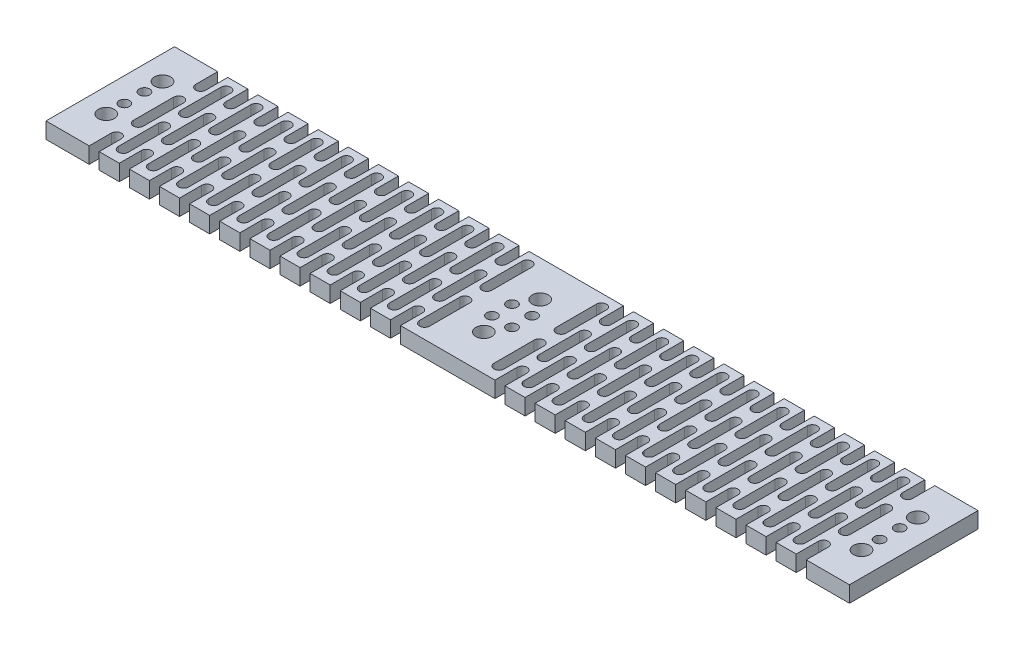
SolidWorks part; units mm, degrees
ref_plane "정면" through (0, 0, 0) normal (0, 0, 1) x (1, 0, 0)
ref_plane "윗면" through (0, 0, 0) normal (0, 1, 0) x (1, 0, 0)
ref_plane "우측면" through (0, 0, 0) normal (1, 0, 0) x (0, 0, -1)
sketch "스케치1" plane through (0, 0, 0) normal (0, 1, 0) x (1, 0, 0)
  line L1 (-50, 8) -> (50, 8)
  line L2 (-50, 8) -> (-50, -8)
  line L3 (-50, -8) -> (50, -8)
  line L4 (50, 8) -> (50, -8)
  dimension "D3" = 50
  dimension "D1" = 16
  dimension "D2" = 100
  dimension "D4" = 8
extrude "보스-돌출1" add sketch "스케치1" along normal blind 2 contours L1 L4 L3 L2
sketch "스케치2" plane through (0, 2, 0) normal (0, 1, 0) x (1, 0, 0)
  line L4 (50, 8) -> (50, -8) construction
  line L5 (-52.7608, 0) -> (58.8086, 0) construction
  line L6 (0, 14.085) -> (0, -13.5662) construction
  circle A2 centre (47, 3.5) radius 1
  circle A3 centre (0, 3.5) radius 1
  circle A4 centre (-47, 3.5) radius 1
  circle A8 centre (47, 1.25) radius 0.65
  circle A11 centre (-47, 1.25) radius 0.65
  circle A12 centre (47, -6.5) radius 1 [skipped]
  circle A13 centre (0, -6.5) radius 1 [skipped]
  circle A14 centre (-47, -6.5) radius 1 [skipped]
  circle A16 centre (1.25, 1.25) radius 0.65
  circle A17 centre (-1.25, 1.25) radius 0.65
  circle A18 centre (47, -1.25) radius 0.65
  circle A19 centre (47, -3.5) radius 1
  circle A20 centre (-1.25, -1.25) radius 0.65
  circle A21 centre (1.25, -1.25) radius 0.65
  circle A22 centre (0, -3.5) radius 1
  circle A23 centre (-47, -1.25) radius 0.65
  circle A24 centre (-47, -3.5) radius 1
  dimension "D4" = 2
  dimension "D9" = 1.3
  dimension "D11" = 2
  dimension "D5" = 3
  dimension "D6" = 3.5
  dimension "D10" = 1.25
  dimension "D12" = 2
  dimension "D7" = 3
  dimension "D8" = 2
extrude "컷-돌출1" cut sketch "스케치2" against normal through all
sketch "스케치3" plane through (0, 2, 0) normal (0, 1, 0) x (1, 0, 0)
  line L0 (44, 2.5) -> (44, -2.5) construction
  line L1 (44.625, 2.5) -> (44.625, -2.5)
  line L2 (43.375, 2.5) -> (43.375, -2.5)
  line L3 (-50, 8) -> (50, 8) construction
  line L4 (50, 8) -> (50, -8) construction
  line L5 (40.25, 2.5) -> (40.25, -2.5) construction
  line L6 (40.875, 2.5) -> (40.875, -2.5)
  line L7 (39.625, 2.5) -> (39.625, -2.5)
  line L8 (36.5, 2.5) -> (36.5, -2.5) construction
  line L9 (37.125, 2.5) -> (37.125, -2.5)
  line L10 (35.875, 2.5) -> (35.875, -2.5)
  line L11 (32.75, 2.5) -> (32.75, -2.5) construction
  line L12 (33.375, 2.5) -> (33.375, -2.5)
  line L13 (32.125, 2.5) -> (32.125, -2.5)
  line L14 (29, 2.5) -> (29, -2.5) construction
  line L15 (29.625, 2.5) -> (29.625, -2.5)
  line L16 (28.375, 2.5) -> (28.375, -2.5)
  line L17 (25.25, 2.5) -> (25.25, -2.5) construction
  line L18 (25.875, 2.5) -> (25.875, -2.5)
  line L19 (24.625, 2.5) -> (24.625, -2.5)
  line L20 (21.5, 2.5) -> (21.5, -2.5) construction
  line L21 (22.125, 2.5) -> (22.125, -2.5)
  line L22 (20.875, 2.5) -> (20.875, -2.5)
  line L23 (17.75, 2.5) -> (17.75, -2.5) construction
  line L24 (18.375, 2.5) -> (18.375, -2.5)
  line L25 (17.125, 2.5) -> (17.125, -2.5)
  line L26 (14, 2.5) -> (14, -2.5) construction
  line L27 (14.625, 2.5) -> (14.625, -2.5)
  line L28 (13.375, 2.5) -> (13.375, -2.5)
  line L29 (10.25, 2.5) -> (10.25, -2.5) construction
  line L30 (10.875, 2.5) -> (10.875, -2.5)
  line L31 (9.625, 2.5) -> (9.625, -2.5)
  line L32 (6.5, 2.5) -> (6.5, -2.5) construction
  line L33 (7.125, 2.5) -> (7.125, -2.5)
  line L34 (5.875, 2.5) -> (5.875, -2.5)
  line L35 (40.25, 10.25) -> (40.25, 5.25) construction
  line L36 (40.875, 10.25) -> (40.875, 5.25)
  line L37 (39.625, 10.25) -> (39.625, 5.25)
  line L38 (36.5, 10.25) -> (36.5, 5.25) construction
  line L39 (37.125, 10.25) -> (37.125, 5.25)
  line L40 (35.875, 10.25) -> (35.875, 5.25)
  line L41 (32.75, 10.25) -> (32.75, 5.25) construction
  line L42 (33.375, 10.25) -> (33.375, 5.25)
  line L43 (32.125, 10.25) -> (32.125, 5.25)
  line L44 (29, 10.25) -> (29, 5.25) construction
  line L45 (29.625, 10.25) -> (29.625, 5.25)
  line L46 (28.375, 10.25) -> (28.375, 5.25)
  line L47 (25.25, 10.25) -> (25.25, 5.25) construction
  line L48 (25.875, 10.25) -> (25.875, 5.25)
  line L49 (24.625, 10.25) -> (24.625, 5.25)
  line L50 (21.5, 10.25) -> (21.5, 5.25) construction
  line L51 (22.125, 10.25) -> (22.125, 5.25)
  line L52 (20.875, 10.25) -> (20.875, 5.25)
  line L53 (17.75, 10.25) -> (17.75, 5.25) construction
  line L54 (18.375, 10.25) -> (18.375, 5.25)
  line L55 (17.125, 10.25) -> (17.125, 5.25)
  line L56 (14, 10.25) -> (14, 5.25) construction
  line L57 (14.625, 10.25) -> (14.625, 5.25)
  line L58 (13.375, 10.25) -> (13.375, 5.25)
  line L59 (10.25, 10.25) -> (10.25, 5.25) construction
  line L60 (10.875, 10.25) -> (10.875, 5.25)
  line L61 (9.625, 10.25) -> (9.625, 5.25)
  line L62 (6.5, 10.25) -> (6.5, 5.25) construction
  line L63 (7.125, 10.25) -> (7.125, 5.25)
  line L64 (5.875, 10.25) -> (5.875, 5.25)
  line L65 (44, 10.25) -> (44, 5.25) construction
  line L66 (44.625, 10.25) -> (44.625, 5.25)
  line L67 (43.375, 10.25) -> (43.375, 5.25)
  line L68 (0, 0) -> (57.0875, 0) construction
  line L69 (-52.7608, 0) -> (58.8086, 0) construction
  line L70 (44, -10.25) -> (44, -5.25) construction
  line L71 (44.625, -10.25) -> (44.625, -5.25)
  line L72 (43.375, -10.25) -> (43.375, -5.25)
  line L73 (6.5, -10.25) -> (6.5, -5.25) construction
  line L74 (7.125, -10.25) -> (7.125, -5.25)
  line L75 (5.875, -10.25) -> (5.875, -5.25)
  line L76 (10.25, -10.25) -> (10.25, -5.25) construction
  line L77 (10.875, -10.25) -> (10.875, -5.25)
  line L78 (9.625, -10.25) -> (9.625, -5.25)
  line L79 (14, -10.25) -> (14, -5.25) construction
  line L80 (14.625, -10.25) -> (14.625, -5.25)
  line L81 (13.375, -10.25) -> (13.375, -5.25)
  line L82 (17.75, -10.25) -> (17.75, -5.25) construction
  line L83 (18.375, -10.25) -> (18.375, -5.25)
  line L84 (17.125, -10.25) -> (17.125, -5.25)
  line L85 (21.5, -10.25) -> (21.5, -5.25) construction
  line L86 (22.125, -10.25) -> (22.125, -5.25)
  line L87 (20.875, -10.25) -> (20.875, -5.25)
  line L88 (25.25, -10.25) -> (25.25, -5.25) construction
  line L89 (25.875, -10.25) -> (25.875, -5.25)
  line L90 (24.625, -10.25) -> (24.625, -5.25)
  line L91 (29, -10.25) -> (29, -5.25) construction
  line L92 (29.625, -10.25) -> (29.625, -5.25)
  line L93 (28.375, -10.25) -> (28.375, -5.25)
  line L94 (32.75, -10.25) -> (32.75, -5.25) construction
  line L95 (33.375, -10.25) -> (33.375, -5.25)
  line L96 (32.125, -10.25) -> (32.125, -5.25)
  line L97 (36.5, -10.25) -> (36.5, -5.25) construction
  line L98 (37.125, -10.25) -> (37.125, -5.25)
  line L99 (35.875, -10.25) -> (35.875, -5.25)
  line L100 (40.25, -10.25) -> (40.25, -5.25) construction
  line L101 (40.875, -10.25) -> (40.875, -5.25)
  line L102 (39.625, -10.25) -> (39.625, -5.25)
  line L103 (42.125, -1.25) -> (42.125, -6.25) construction
  line L104 (42.75, -1.25) -> (42.75, -6.25)
  line L105 (41.5, -1.25) -> (41.5, -6.25)
  line L106 (38.375, -1.25) -> (38.375, -6.25) construction
  line L107 (39, -1.25) -> (39, -6.25)
  line L108 (37.75, -1.25) -> (37.75, -6.25)
  line L109 (34.625, -1.25) -> (34.625, -6.25) construction
  line L110 (35.25, -1.25) -> (35.25, -6.25)
  line L111 (34, -1.25) -> (34, -6.25)
  line L112 (30.875, -1.25) -> (30.875, -6.25) construction
  line L113 (31.5, -1.25) -> (31.5, -6.25)
  line L114 (30.25, -1.25) -> (30.25, -6.25)
  line L115 (27.125, -1.25) -> (27.125, -6.25) construction
  line L116 (27.75, -1.25) -> (27.75, -6.25)
  line L117 (26.5, -1.25) -> (26.5, -6.25)
  line L118 (23.375, -1.25) -> (23.375, -6.25) construction
  line L119 (24, -1.25) -> (24, -6.25)
  line L120 (22.75, -1.25) -> (22.75, -6.25)
  line L121 (19.625, -1.25) -> (19.625, -6.25) construction
  line L122 (20.25, -1.25) -> (20.25, -6.25)
  line L123 (19, -1.25) -> (19, -6.25)
  line L124 (15.875, -1.25) -> (15.875, -6.25) construction
  line L125 (16.5, -1.25) -> (16.5, -6.25)
  line L126 (15.25, -1.25) -> (15.25, -6.25)
  line L127 (12.125, -1.25) -> (12.125, -6.25) construction
  line L128 (12.75, -1.25) -> (12.75, -6.25)
  line L129 (11.5, -1.25) -> (11.5, -6.25)
  line L130 (8.375, -1.25) -> (8.375, -6.25) construction
  line L131 (9, -1.25) -> (9, -6.25)
  line L132 (7.75, -1.25) -> (7.75, -6.25)
  line L133 (4.625, -1.25) -> (4.625, -6.25) construction
  line L134 (5.25, -1.25) -> (5.25, -6.25)
  line L135 (4, -1.25) -> (4, -6.25)
  line L136 (38.375, 6.5) -> (38.375, 1.5) construction
  line L137 (39, 6.5) -> (39, 1.5)
  line L138 (37.75, 6.5) -> (37.75, 1.5)
  line L139 (34.625, 6.5) -> (34.625, 1.5) construction
  line L140 (35.25, 6.5) -> (35.25, 1.5)
  line L141 (34, 6.5) -> (34, 1.5)
  line L142 (30.875, 6.5) -> (30.875, 1.5) construction
  line L143 (31.5, 6.5) -> (31.5, 1.5)
  line L144 (30.25, 6.5) -> (30.25, 1.5)
  line L145 (27.125, 6.5) -> (27.125, 1.5) construction
  line L146 (27.75, 6.5) -> (27.75, 1.5)
  line L147 (26.5, 6.5) -> (26.5, 1.5)
  line L148 (23.375, 6.5) -> (23.375, 1.5) construction
  line L149 (24, 6.5) -> (24, 1.5)
  line L150 (22.75, 6.5) -> (22.75, 1.5)
  line L151 (19.625, 6.5) -> (19.625, 1.5) construction
  line L152 (20.25, 6.5) -> (20.25, 1.5)
  line L153 (19, 6.5) -> (19, 1.5)
  line L154 (15.875, 6.5) -> (15.875, 1.5) construction
  line L155 (16.5, 6.5) -> (16.5, 1.5)
  line L156 (15.25, 6.5) -> (15.25, 1.5)
  line L157 (12.125, 6.5) -> (12.125, 1.5) construction
  line L158 (12.75, 6.5) -> (12.75, 1.5)
  line L159 (11.5, 6.5) -> (11.5, 1.5)
  line L160 (8.375, 6.5) -> (8.375, 1.5) construction
  line L161 (9, 6.5) -> (9, 1.5)
  line L162 (7.75, 6.5) -> (7.75, 1.5)
  line L163 (4.625, 6.5) -> (4.625, 1.5) construction
  line L164 (5.25, 6.5) -> (5.25, 1.5)
  line L165 (4, 6.5) -> (4, 1.5)
  line L166 (42.125, 6.5) -> (42.125, 1.5) construction
  line L167 (42.75, 6.5) -> (42.75, 1.5)
  line L168 (41.5, 6.5) -> (41.5, 1.5)
  line L169 (0, 14.085) -> (0, -13.5662) construction
  line L170 (-42.125, 6.5) -> (-42.125, 1.5) construction
  line L171 (-42.75, 6.5) -> (-42.75, 1.5)
  line L172 (-41.5, 6.5) -> (-41.5, 1.5)
  line L173 (-4.625, 6.5) -> (-4.625, 1.5) construction
  line L174 (-5.25, 6.5) -> (-5.25, 1.5)
  line L175 (-4, 6.5) -> (-4, 1.5)
  line L176 (-8.375, 6.5) -> (-8.375, 1.5) construction
  line L177 (-9, 6.5) -> (-9, 1.5)
  line L178 (-7.75, 6.5) -> (-7.75, 1.5)
  line L179 (-12.125, 6.5) -> (-12.125, 1.5) construction
  line L180 (-12.75, 6.5) -> (-12.75, 1.5)
  line L181 (-11.5, 6.5) -> (-11.5, 1.5)
  line L182 (-15.875, 6.5) -> (-15.875, 1.5) construction
  line L183 (-16.5, 6.5) -> (-16.5, 1.5)
  line L184 (-15.25, 6.5) -> (-15.25, 1.5)
  line L185 (-19.625, 6.5) -> (-19.625, 1.5) construction
  line L186 (-20.25, 6.5) -> (-20.25, 1.5)
  line L187 (-19, 6.5) -> (-19, 1.5)
  line L188 (-23.375, 6.5) -> (-23.375, 1.5) construction
  line L189 (-24, 6.5) -> (-24, 1.5)
  line L190 (-22.75, 6.5) -> (-22.75, 1.5)
  line L191 (-27.125, 6.5) -> (-27.125, 1.5) construction
  line L192 (-27.75, 6.5) -> (-27.75, 1.5)
  line L193 (-26.5, 6.5) -> (-26.5, 1.5)
  line L194 (-30.875, 6.5) -> (-30.875, 1.5) construction
  line L195 (-31.5, 6.5) -> (-31.5, 1.5)
  line L196 (-30.25, 6.5) -> (-30.25, 1.5)
  line L197 (-34.625, 6.5) -> (-34.625, 1.5) construction
  line L198 (-35.25, 6.5) -> (-35.25, 1.5)
  line L199 (-34, 6.5) -> (-34, 1.5)
  line L200 (-38.375, 6.5) -> (-38.375, 1.5) construction
  line L201 (-39, 6.5) -> (-39, 1.5)
  line L202 (-37.75, 6.5) -> (-37.75, 1.5)
  line L203 (-4.625, -1.25) -> (-4.625, -6.25) construction
  line L204 (-5.25, -1.25) -> (-5.25, -6.25)
  line L205 (-4, -1.25) -> (-4, -6.25)
  line L206 (-8.375, -1.25) -> (-8.375, -6.25) construction
  line L207 (-9, -1.25) -> (-9, -6.25)
  line L208 (-7.75, -1.25) -> (-7.75, -6.25)
  line L209 (-12.125, -1.25) -> (-12.125, -6.25) construction
  line L210 (-12.75, -1.25) -> (-12.75, -6.25)
  line L211 (-11.5, -1.25) -> (-11.5, -6.25)
  line L212 (-15.875, -1.25) -> (-15.875, -6.25) construction
  line L213 (-16.5, -1.25) -> (-16.5, -6.25)
  line L214 (-15.25, -1.25) -> (-15.25, -6.25)
  line L215 (-19.625, -1.25) -> (-19.625, -6.25) construction
  line L216 (-20.25, -1.25) -> (-20.25, -6.25)
  line L217 (-19, -1.25) -> (-19, -6.25)
  line L218 (-23.375, -1.25) -> (-23.375, -6.25) construction
  line L219 (-24, -1.25) -> (-24, -6.25)
  line L220 (-22.75, -1.25) -> (-22.75, -6.25)
  line L221 (-27.125, -1.25) -> (-27.125, -6.25) construction
  line L222 (-27.75, -1.25) -> (-27.75, -6.25)
  line L223 (-26.5, -1.25) -> (-26.5, -6.25)
  line L224 (-30.875, -1.25) -> (-30.875, -6.25) construction
  line L225 (-31.5, -1.25) -> (-31.5, -6.25)
  line L226 (-30.25, -1.25) -> (-30.25, -6.25)
  line L227 (-34.625, -1.25) -> (-34.625, -6.25) construction
  line L228 (-35.25, -1.25) -> (-35.25, -6.25)
  line L229 (-34, -1.25) -> (-34, -6.25)
  line L230 (-38.375, -1.25) -> (-38.375, -6.25) construction
  line L231 (-39, -1.25) -> (-39, -6.25)
  line L232 (-37.75, -1.25) -> (-37.75, -6.25)
  line L233 (-42.125, -1.25) -> (-42.125, -6.25) construction
  line L234 (-42.75, -1.25) -> (-42.75, -6.25)
  line L235 (-41.5, -1.25) -> (-41.5, -6.25)
  line L236 (-40.25, -10.25) -> (-40.25, -5.25) construction
  line L237 (-40.875, -10.25) -> (-40.875, -5.25)
  line L238 (-39.625, -10.25) -> (-39.625, -5.25)
  line L239 (-36.5, -10.25) -> (-36.5, -5.25) construction
  line L240 (-37.125, -10.25) -> (-37.125, -5.25)
  line L241 (-35.875, -10.25) -> (-35.875, -5.25)
  line L242 (-32.75, -10.25) -> (-32.75, -5.25) construction
  line L243 (-33.375, -10.25) -> (-33.375, -5.25)
  line L244 (-32.125, -10.25) -> (-32.125, -5.25)
  line L245 (-29, -10.25) -> (-29, -5.25) construction
  line L246 (-29.625, -10.25) -> (-29.625, -5.25)
  line L247 (-28.375, -10.25) -> (-28.375, -5.25)
  line L248 (-25.25, -10.25) -> (-25.25, -5.25) construction
  line L249 (-25.875, -10.25) -> (-25.875, -5.25)
  line L250 (-24.625, -10.25) -> (-24.625, -5.25)
  line L251 (-21.5, -10.25) -> (-21.5, -5.25) construction
  line L252 (-22.125, -10.25) -> (-22.125, -5.25)
  line L253 (-20.875, -10.25) -> (-20.875, -5.25)
  line L254 (-17.75, -10.25) -> (-17.75, -5.25) construction
  line L255 (-18.375, -10.25) -> (-18.375, -5.25)
  line L256 (-17.125, -10.25) -> (-17.125, -5.25)
  line L257 (-14, -10.25) -> (-14, -5.25) construction
  line L258 (-14.625, -10.25) -> (-14.625, -5.25)
  line L259 (-13.375, -10.25) -> (-13.375, -5.25)
  line L260 (-10.25, -10.25) -> (-10.25, -5.25) construction
  line L261 (-10.875, -10.25) -> (-10.875, -5.25)
  line L262 (-9.625, -10.25) -> (-9.625, -5.25)
  line L263 (-6.5, -10.25) -> (-6.5, -5.25) construction
  line L264 (-7.125, -10.25) -> (-7.125, -5.25)
  line L265 (-5.875, -10.25) -> (-5.875, -5.25)
  line L266 (-44, -10.25) -> (-44, -5.25) construction
  line L267 (-44.625, -10.25) -> (-44.625, -5.25)
  line L268 (-43.375, -10.25) -> (-43.375, -5.25)
  line L269 (-44, 10.25) -> (-44, 5.25) construction
  line L270 (-44.625, 10.25) -> (-44.625, 5.25)
  line L271 (-43.375, 10.25) -> (-43.375, 5.25)
  line L272 (-6.5, 10.25) -> (-6.5, 5.25) construction
  line L273 (-7.125, 10.25) -> (-7.125, 5.25)
  line L274 (-5.875, 10.25) -> (-5.875, 5.25)
  line L275 (-10.25, 10.25) -> (-10.25, 5.25) construction
  line L276 (-10.875, 10.25) -> (-10.875, 5.25)
  line L277 (-9.625, 10.25) -> (-9.625, 5.25)
  line L278 (-14, 10.25) -> (-14, 5.25) construction
  line L279 (-14.625, 10.25) -> (-14.625, 5.25)
  line L280 (-13.375, 10.25) -> (-13.375, 5.25)
  line L281 (-17.75, 10.25) -> (-17.75, 5.25) construction
  line L282 (-18.375, 10.25) -> (-18.375, 5.25)
  line L283 (-17.125, 10.25) -> (-17.125, 5.25)
  line L284 (-21.5, 10.25) -> (-21.5, 5.25) construction
  line L285 (-22.125, 10.25) -> (-22.125, 5.25)
  line L286 (-20.875, 10.25) -> (-20.875, 5.25)
  line L287 (-25.25, 10.25) -> (-25.25, 5.25) construction
  line L288 (-25.875, 10.25) -> (-25.875, 5.25)
  line L289 (-24.625, 10.25) -> (-24.625, 5.25)
  line L290 (-29, 10.25) -> (-29, 5.25) construction
  line L291 (-29.625, 10.25) -> (-29.625, 5.25)
  line L292 (-28.375, 10.25) -> (-28.375, 5.25)
  line L293 (-32.75, 10.25) -> (-32.75, 5.25) construction
  line L294 (-33.375, 10.25) -> (-33.375, 5.25)
  line L295 (-32.125, 10.25) -> (-32.125, 5.25)
  line L296 (-36.5, 10.25) -> (-36.5, 5.25) construction
  line L297 (-37.125, 10.25) -> (-37.125, 5.25)
  line L298 (-35.875, 10.25) -> (-35.875, 5.25)
  line L299 (-40.25, 10.25) -> (-40.25, 5.25) construction
  line L300 (-40.875, 10.25) -> (-40.875, 5.25)
  line L301 (-39.625, 10.25) -> (-39.625, 5.25)
  line L302 (-6.5, 2.5) -> (-6.5, -2.5) construction
  line L303 (-7.125, 2.5) -> (-7.125, -2.5)
  line L304 (-5.875, 2.5) -> (-5.875, -2.5)
  line L305 (-10.25, 2.5) -> (-10.25, -2.5) construction
  line L306 (-10.875, 2.5) -> (-10.875, -2.5)
  line L307 (-9.625, 2.5) -> (-9.625, -2.5)
  line L308 (-14, 2.5) -> (-14, -2.5) construction
  line L309 (-14.625, 2.5) -> (-14.625, -2.5)
  line L310 (-13.375, 2.5) -> (-13.375, -2.5)
  line L311 (-17.75, 2.5) -> (-17.75, -2.5) construction
  line L312 (-18.375, 2.5) -> (-18.375, -2.5)
  line L313 (-17.125, 2.5) -> (-17.125, -2.5)
  line L314 (-21.5, 2.5) -> (-21.5, -2.5) construction
  line L315 (-22.125, 2.5) -> (-22.125, -2.5)
  line L316 (-20.875, 2.5) -> (-20.875, -2.5)
  line L317 (-25.25, 2.5) -> (-25.25, -2.5) construction
  line L318 (-25.875, 2.5) -> (-25.875, -2.5)
  line L319 (-24.625, 2.5) -> (-24.625, -2.5)
  line L320 (-29, 2.5) -> (-29, -2.5) construction
  line L321 (-29.625, 2.5) -> (-29.625, -2.5)
  line L322 (-28.375, 2.5) -> (-28.375, -2.5)
  line L323 (-32.75, 2.5) -> (-32.75, -2.5) construction
  line L324 (-33.375, 2.5) -> (-33.375, -2.5)
  line L325 (-32.125, 2.5) -> (-32.125, -2.5)
  line L326 (-36.5, 2.5) -> (-36.5, -2.5) construction
  line L327 (-37.125, 2.5) -> (-37.125, -2.5)
  line L328 (-35.875, 2.5) -> (-35.875, -2.5)
  line L329 (-40.25, 2.5) -> (-40.25, -2.5) construction
  line L330 (-40.875, 2.5) -> (-40.875, -2.5)
  line L331 (-39.625, 2.5) -> (-39.625, -2.5)
  line L332 (-44, 2.5) -> (-44, -2.5) construction
  line L333 (-44.625, 2.5) -> (-44.625, -2.5)
  line L334 (-43.375, 2.5) -> (-43.375, -2.5)
  arc A0 (44.625, 2.5) -> (43.375, 2.5) centre (44, 2.5) ccw
  arc A1 (43.375, -2.5) -> (44.625, -2.5) centre (44, -2.5) ccw
  arc A2 (40.875, 2.5) -> (39.625, 2.5) centre (40.25, 2.5) ccw
  arc A3 (39.625, -2.5) -> (40.875, -2.5) centre (40.25, -2.5) ccw
  arc A4 (37.125, 2.5) -> (35.875, 2.5) centre (36.5, 2.5) ccw
  arc A5 (35.875, -2.5) -> (37.125, -2.5) centre (36.5, -2.5) ccw
  arc A6 (33.375, 2.5) -> (32.125, 2.5) centre (32.75, 2.5) ccw
  arc A7 (32.125, -2.5) -> (33.375, -2.5) centre (32.75, -2.5) ccw
  arc A8 (29.625, 2.5) -> (28.375, 2.5) centre (29, 2.5) ccw
  arc A9 (28.375, -2.5) -> (29.625, -2.5) centre (29, -2.5) ccw
  arc A10 (25.875, 2.5) -> (24.625, 2.5) centre (25.25, 2.5) ccw
  arc A11 (24.625, -2.5) -> (25.875, -2.5) centre (25.25, -2.5) ccw
  arc A12 (22.125, 2.5) -> (20.875, 2.5) centre (21.5, 2.5) ccw
  arc A13 (20.875, -2.5) -> (22.125, -2.5) centre (21.5, -2.5) ccw
  arc A14 (18.375, 2.5) -> (17.125, 2.5) centre (17.75, 2.5) ccw
  arc A15 (17.125, -2.5) -> (18.375, -2.5) centre (17.75, -2.5) ccw
  arc A16 (14.625, 2.5) -> (13.375, 2.5) centre (14, 2.5) ccw
  arc A17 (13.375, -2.5) -> (14.625, -2.5) centre (14, -2.5) ccw
  arc A18 (10.875, 2.5) -> (9.625, 2.5) centre (10.25, 2.5) ccw
  arc A19 (9.625, -2.5) -> (10.875, -2.5) centre (10.25, -2.5) ccw
  arc A20 (7.125, 2.5) -> (5.875, 2.5) centre (6.5, 2.5) ccw
  arc A21 (5.875, -2.5) -> (7.125, -2.5) centre (6.5, -2.5) ccw
  arc A22 (40.875, 10.25) -> (39.625, 10.25) centre (40.25, 10.25) ccw
  arc A23 (39.625, 5.25) -> (40.875, 5.25) centre (40.25, 5.25) ccw
  arc A24 (37.125, 10.25) -> (35.875, 10.25) centre (36.5, 10.25) ccw
  arc A25 (35.875, 5.25) -> (37.125, 5.25) centre (36.5, 5.25) ccw
  arc A26 (33.375, 10.25) -> (32.125, 10.25) centre (32.75, 10.25) ccw
  arc A27 (32.125, 5.25) -> (33.375, 5.25) centre (32.75, 5.25) ccw
  arc A28 (29.625, 10.25) -> (28.375, 10.25) centre (29, 10.25) ccw
  arc A29 (28.375, 5.25) -> (29.625, 5.25) centre (29, 5.25) ccw
  arc A30 (25.875, 10.25) -> (24.625, 10.25) centre (25.25, 10.25) ccw
  arc A31 (24.625, 5.25) -> (25.875, 5.25) centre (25.25, 5.25) ccw
  arc A32 (22.125, 10.25) -> (20.875, 10.25) centre (21.5, 10.25) ccw
  arc A33 (20.875, 5.25) -> (22.125, 5.25) centre (21.5, 5.25) ccw
  arc A34 (18.375, 10.25) -> (17.125, 10.25) centre (17.75, 10.25) ccw
  arc A35 (17.125, 5.25) -> (18.375, 5.25) centre (17.75, 5.25) ccw
  arc A36 (14.625, 10.25) -> (13.375, 10.25) centre (14, 10.25) ccw
  arc A37 (13.375, 5.25) -> (14.625, 5.25) centre (14, 5.25) ccw
  arc A38 (10.875, 10.25) -> (9.625, 10.25) centre (10.25, 10.25) ccw
  arc A39 (9.625, 5.25) -> (10.875, 5.25) centre (10.25, 5.25) ccw
  arc A40 (7.125, 10.25) -> (5.875, 10.25) centre (6.5, 10.25) ccw
  arc A41 (5.875, 5.25) -> (7.125, 5.25) centre (6.5, 5.25) ccw
  arc A42 (44.625, 10.25) -> (43.375, 10.25) centre (44, 10.25) ccw
  arc A43 (43.375, 5.25) -> (44.625, 5.25) centre (44, 5.25) ccw
  arc A44 (44.625, -10.25) -> (43.375, -10.25) centre (44, -10.25) cw
  arc A45 (43.375, -5.25) -> (44.625, -5.25) centre (44, -5.25) cw
  arc A46 (7.125, -10.25) -> (5.875, -10.25) centre (6.5, -10.25) cw
  arc A47 (5.875, -5.25) -> (7.125, -5.25) centre (6.5, -5.25) cw
  arc A48 (10.875, -10.25) -> (9.625, -10.25) centre (10.25, -10.25) cw
  arc A49 (9.625, -5.25) -> (10.875, -5.25) centre (10.25, -5.25) cw
  arc A50 (14.625, -10.25) -> (13.375, -10.25) centre (14, -10.25) cw
  arc A51 (13.375, -5.25) -> (14.625, -5.25) centre (14, -5.25) cw
  arc A52 (18.375, -10.25) -> (17.125, -10.25) centre (17.75, -10.25) cw
  arc A53 (17.125, -5.25) -> (18.375, -5.25) centre (17.75, -5.25) cw
  arc A54 (22.125, -10.25) -> (20.875, -10.25) centre (21.5, -10.25) cw
  arc A55 (20.875, -5.25) -> (22.125, -5.25) centre (21.5, -5.25) cw
  arc A56 (25.875, -10.25) -> (24.625, -10.25) centre (25.25, -10.25) cw
  arc A57 (24.625, -5.25) -> (25.875, -5.25) centre (25.25, -5.25) cw
  arc A58 (29.625, -10.25) -> (28.375, -10.25) centre (29, -10.25) cw
  arc A59 (28.375, -5.25) -> (29.625, -5.25) centre (29, -5.25) cw
  arc A60 (33.375, -10.25) -> (32.125, -10.25) centre (32.75, -10.25) cw
  arc A61 (32.125, -5.25) -> (33.375, -5.25) centre (32.75, -5.25) cw
  arc A62 (37.125, -10.25) -> (35.875, -10.25) centre (36.5, -10.25) cw
  arc A63 (35.875, -5.25) -> (37.125, -5.25) centre (36.5, -5.25) cw
  arc A64 (40.875, -10.25) -> (39.625, -10.25) centre (40.25, -10.25) cw
  arc A65 (39.625, -5.25) -> (40.875, -5.25) centre (40.25, -5.25) cw
  arc A66 (42.75, -1.25) -> (41.5, -1.25) centre (42.125, -1.25) ccw
  arc A67 (41.5, -6.25) -> (42.75, -6.25) centre (42.125, -6.25) ccw
  arc A68 (39, -1.25) -> (37.75, -1.25) centre (38.375, -1.25) ccw
  arc A69 (37.75, -6.25) -> (39, -6.25) centre (38.375, -6.25) ccw
  arc A70 (35.25, -1.25) -> (34, -1.25) centre (34.625, -1.25) ccw
  arc A71 (34, -6.25) -> (35.25, -6.25) centre (34.625, -6.25) ccw
  arc A72 (31.5, -1.25) -> (30.25, -1.25) centre (30.875, -1.25) ccw
  arc A73 (30.25, -6.25) -> (31.5, -6.25) centre (30.875, -6.25) ccw
  arc A74 (27.75, -1.25) -> (26.5, -1.25) centre (27.125, -1.25) ccw
  arc A75 (26.5, -6.25) -> (27.75, -6.25) centre (27.125, -6.25) ccw
  arc A76 (24, -1.25) -> (22.75, -1.25) centre (23.375, -1.25) ccw
  arc A77 (22.75, -6.25) -> (24, -6.25) centre (23.375, -6.25) ccw
  arc A78 (20.25, -1.25) -> (19, -1.25) centre (19.625, -1.25) ccw
  arc A79 (19, -6.25) -> (20.25, -6.25) centre (19.625, -6.25) ccw
  arc A80 (16.5, -1.25) -> (15.25, -1.25) centre (15.875, -1.25) ccw
  arc A81 (15.25, -6.25) -> (16.5, -6.25) centre (15.875, -6.25) ccw
  arc A82 (12.75, -1.25) -> (11.5, -1.25) centre (12.125, -1.25) ccw
  arc A83 (11.5, -6.25) -> (12.75, -6.25) centre (12.125, -6.25) ccw
  arc A84 (9, -1.25) -> (7.75, -1.25) centre (8.375, -1.25) ccw
  arc A85 (7.75, -6.25) -> (9, -6.25) centre (8.375, -6.25) ccw
  arc A86 (5.25, -1.25) -> (4, -1.25) centre (4.625, -1.25) ccw
  arc A87 (4, -6.25) -> (5.25, -6.25) centre (4.625, -6.25) ccw
  arc A88 (39, 6.5) -> (37.75, 6.5) centre (38.375, 6.5) ccw
  arc A89 (37.75, 1.5) -> (39, 1.5) centre (38.375, 1.5) ccw
  arc A90 (35.25, 6.5) -> (34, 6.5) centre (34.625, 6.5) ccw
  arc A91 (34, 1.5) -> (35.25, 1.5) centre (34.625, 1.5) ccw
  arc A92 (31.5, 6.5) -> (30.25, 6.5) centre (30.875, 6.5) ccw
  arc A93 (30.25, 1.5) -> (31.5, 1.5) centre (30.875, 1.5) ccw
  arc A94 (27.75, 6.5) -> (26.5, 6.5) centre (27.125, 6.5) ccw
  arc A95 (26.5, 1.5) -> (27.75, 1.5) centre (27.125, 1.5) ccw
  arc A96 (24, 6.5) -> (22.75, 6.5) centre (23.375, 6.5) ccw
  arc A97 (22.75, 1.5) -> (24, 1.5) centre (23.375, 1.5) ccw
  arc A98 (20.25, 6.5) -> (19, 6.5) centre (19.625, 6.5) ccw
  arc A99 (19, 1.5) -> (20.25, 1.5) centre (19.625, 1.5) ccw
  arc A100 (16.5, 6.5) -> (15.25, 6.5) centre (15.875, 6.5) ccw
  arc A101 (15.25, 1.5) -> (16.5, 1.5) centre (15.875, 1.5) ccw
  arc A102 (12.75, 6.5) -> (11.5, 6.5) centre (12.125, 6.5) ccw
  arc A103 (11.5, 1.5) -> (12.75, 1.5) centre (12.125, 1.5) ccw
  arc A104 (9, 6.5) -> (7.75, 6.5) centre (8.375, 6.5) ccw
  arc A105 (7.75, 1.5) -> (9, 1.5) centre (8.375, 1.5) ccw
  arc A106 (5.25, 6.5) -> (4, 6.5) centre (4.625, 6.5) ccw
  arc A107 (4, 1.5) -> (5.25, 1.5) centre (4.625, 1.5) ccw
  arc A108 (42.75, 6.5) -> (41.5, 6.5) centre (42.125, 6.5) ccw
  arc A109 (41.5, 1.5) -> (42.75, 1.5) centre (42.125, 1.5) ccw
  arc A110 (-42.75, 6.5) -> (-41.5, 6.5) centre (-42.125, 6.5) cw
  arc A111 (-41.5, 1.5) -> (-42.75, 1.5) centre (-42.125, 1.5) cw
  arc A112 (-5.25, 6.5) -> (-4, 6.5) centre (-4.625, 6.5) cw
  arc A113 (-4, 1.5) -> (-5.25, 1.5) centre (-4.625, 1.5) cw
  arc A114 (-9, 6.5) -> (-7.75, 6.5) centre (-8.375, 6.5) cw
  arc A115 (-7.75, 1.5) -> (-9, 1.5) centre (-8.375, 1.5) cw
  arc A116 (-12.75, 6.5) -> (-11.5, 6.5) centre (-12.125, 6.5) cw
  arc A117 (-11.5, 1.5) -> (-12.75, 1.5) centre (-12.125, 1.5) cw
  arc A118 (-16.5, 6.5) -> (-15.25, 6.5) centre (-15.875, 6.5) cw
  arc A119 (-15.25, 1.5) -> (-16.5, 1.5) centre (-15.875, 1.5) cw
  arc A120 (-20.25, 6.5) -> (-19, 6.5) centre (-19.625, 6.5) cw
  arc A121 (-19, 1.5) -> (-20.25, 1.5) centre (-19.625, 1.5) cw
  arc A122 (-24, 6.5) -> (-22.75, 6.5) centre (-23.375, 6.5) cw
  arc A123 (-22.75, 1.5) -> (-24, 1.5) centre (-23.375, 1.5) cw
  arc A124 (-27.75, 6.5) -> (-26.5, 6.5) centre (-27.125, 6.5) cw
  arc A125 (-26.5, 1.5) -> (-27.75, 1.5) centre (-27.125, 1.5) cw
  arc A126 (-31.5, 6.5) -> (-30.25, 6.5) centre (-30.875, 6.5) cw
  arc A127 (-30.25, 1.5) -> (-31.5, 1.5) centre (-30.875, 1.5) cw
  arc A128 (-35.25, 6.5) -> (-34, 6.5) centre (-34.625, 6.5) cw
  arc A129 (-34, 1.5) -> (-35.25, 1.5) centre (-34.625, 1.5) cw
  arc A130 (-39, 6.5) -> (-37.75, 6.5) centre (-38.375, 6.5) cw
  arc A131 (-37.75, 1.5) -> (-39, 1.5) centre (-38.375, 1.5) cw
  arc A132 (-5.25, -1.25) -> (-4, -1.25) centre (-4.625, -1.25) cw
  arc A133 (-4, -6.25) -> (-5.25, -6.25) centre (-4.625, -6.25) cw
  arc A134 (-9, -1.25) -> (-7.75, -1.25) centre (-8.375, -1.25) cw
  arc A135 (-7.75, -6.25) -> (-9, -6.25) centre (-8.375, -6.25) cw
  arc A136 (-12.75, -1.25) -> (-11.5, -1.25) centre (-12.125, -1.25) cw
  arc A137 (-11.5, -6.25) -> (-12.75, -6.25) centre (-12.125, -6.25) cw
  arc A138 (-16.5, -1.25) -> (-15.25, -1.25) centre (-15.875, -1.25) cw
  arc A139 (-15.25, -6.25) -> (-16.5, -6.25) centre (-15.875, -6.25) cw
  arc A140 (-20.25, -1.25) -> (-19, -1.25) centre (-19.625, -1.25) cw
  arc A141 (-19, -6.25) -> (-20.25, -6.25) centre (-19.625, -6.25) cw
  arc A142 (-24, -1.25) -> (-22.75, -1.25) centre (-23.375, -1.25) cw
  arc A143 (-22.75, -6.25) -> (-24, -6.25) centre (-23.375, -6.25) cw
  arc A144 (-27.75, -1.25) -> (-26.5, -1.25) centre (-27.125, -1.25) cw
  arc A145 (-26.5, -6.25) -> (-27.75, -6.25) centre (-27.125, -6.25) cw
  arc A146 (-31.5, -1.25) -> (-30.25, -1.25) centre (-30.875, -1.25) cw
  arc A147 (-30.25, -6.25) -> (-31.5, -6.25) centre (-30.875, -6.25) cw
  arc A148 (-35.25, -1.25) -> (-34, -1.25) centre (-34.625, -1.25) cw
  arc A149 (-34, -6.25) -> (-35.25, -6.25) centre (-34.625, -6.25) cw
  arc A150 (-39, -1.25) -> (-37.75, -1.25) centre (-38.375, -1.25) cw
  arc A151 (-37.75, -6.25) -> (-39, -6.25) centre (-38.375, -6.25) cw
  arc A152 (-42.75, -1.25) -> (-41.5, -1.25) centre (-42.125, -1.25) cw
  arc A153 (-41.5, -6.25) -> (-42.75, -6.25) centre (-42.125, -6.25) cw
  arc A154 (-40.875, -10.25) -> (-39.625, -10.25) centre (-40.25, -10.25) ccw
  arc A155 (-39.625, -5.25) -> (-40.875, -5.25) centre (-40.25, -5.25) ccw
  arc A156 (-37.125, -10.25) -> (-35.875, -10.25) centre (-36.5, -10.25) ccw
  arc A157 (-35.875, -5.25) -> (-37.125, -5.25) centre (-36.5, -5.25) ccw
  arc A158 (-33.375, -10.25) -> (-32.125, -10.25) centre (-32.75, -10.25) ccw
  arc A159 (-32.125, -5.25) -> (-33.375, -5.25) centre (-32.75, -5.25) ccw
  arc A160 (-29.625, -10.25) -> (-28.375, -10.25) centre (-29, -10.25) ccw
  arc A161 (-28.375, -5.25) -> (-29.625, -5.25) centre (-29, -5.25) ccw
  arc A162 (-25.875, -10.25) -> (-24.625, -10.25) centre (-25.25, -10.25) ccw
  arc A163 (-24.625, -5.25) -> (-25.875, -5.25) centre (-25.25, -5.25) ccw
  arc A164 (-22.125, -10.25) -> (-20.875, -10.25) centre (-21.5, -10.25) ccw
  arc A165 (-20.875, -5.25) -> (-22.125, -5.25) centre (-21.5, -5.25) ccw
  arc A166 (-18.375, -10.25) -> (-17.125, -10.25) centre (-17.75, -10.25) ccw
  arc A167 (-17.125, -5.25) -> (-18.375, -5.25) centre (-17.75, -5.25) ccw
  arc A168 (-14.625, -10.25) -> (-13.375, -10.25) centre (-14, -10.25) ccw
  arc A169 (-13.375, -5.25) -> (-14.625, -5.25) centre (-14, -5.25) ccw
  arc A170 (-10.875, -10.25) -> (-9.625, -10.25) centre (-10.25, -10.25) ccw
  arc A171 (-9.625, -5.25) -> (-10.875, -5.25) centre (-10.25, -5.25) ccw
  arc A172 (-7.125, -10.25) -> (-5.875, -10.25) centre (-6.5, -10.25) ccw
  arc A173 (-5.875, -5.25) -> (-7.125, -5.25) centre (-6.5, -5.25) ccw
  arc A174 (-44.625, -10.25) -> (-43.375, -10.25) centre (-44, -10.25) ccw
  arc A175 (-43.375, -5.25) -> (-44.625, -5.25) centre (-44, -5.25) ccw
  arc A176 (-44.625, 10.25) -> (-43.375, 10.25) centre (-44, 10.25) cw
  arc A177 (-43.375, 5.25) -> (-44.625, 5.25) centre (-44, 5.25) cw
  arc A178 (-7.125, 10.25) -> (-5.875, 10.25) centre (-6.5, 10.25) cw
  arc A179 (-5.875, 5.25) -> (-7.125, 5.25) centre (-6.5, 5.25) cw
  arc A180 (-10.875, 10.25) -> (-9.625, 10.25) centre (-10.25, 10.25) cw
  arc A181 (-9.625, 5.25) -> (-10.875, 5.25) centre (-10.25, 5.25) cw
  arc A182 (-14.625, 10.25) -> (-13.375, 10.25) centre (-14, 10.25) cw
  arc A183 (-13.375, 5.25) -> (-14.625, 5.25) centre (-14, 5.25) cw
  arc A184 (-18.375, 10.25) -> (-17.125, 10.25) centre (-17.75, 10.25) cw
  arc A185 (-17.125, 5.25) -> (-18.375, 5.25) centre (-17.75, 5.25) cw
  arc A186 (-22.125, 10.25) -> (-20.875, 10.25) centre (-21.5, 10.25) cw
  arc A187 (-20.875, 5.25) -> (-22.125, 5.25) centre (-21.5, 5.25) cw
  arc A188 (-25.875, 10.25) -> (-24.625, 10.25) centre (-25.25, 10.25) cw
  arc A189 (-24.625, 5.25) -> (-25.875, 5.25) centre (-25.25, 5.25) cw
  arc A190 (-29.625, 10.25) -> (-28.375, 10.25) centre (-29, 10.25) cw
  arc A191 (-28.375, 5.25) -> (-29.625, 5.25) centre (-29, 5.25) cw
  arc A192 (-33.375, 10.25) -> (-32.125, 10.25) centre (-32.75, 10.25) cw
  arc A193 (-32.125, 5.25) -> (-33.375, 5.25) centre (-32.75, 5.25) cw
  arc A194 (-37.125, 10.25) -> (-35.875, 10.25) centre (-36.5, 10.25) cw
  arc A195 (-35.875, 5.25) -> (-37.125, 5.25) centre (-36.5, 5.25) cw
  arc A196 (-40.875, 10.25) -> (-39.625, 10.25) centre (-40.25, 10.25) cw
  arc A197 (-39.625, 5.25) -> (-40.875, 5.25) centre (-40.25, 5.25) cw
  arc A198 (-7.125, 2.5) -> (-5.875, 2.5) centre (-6.5, 2.5) cw
  arc A199 (-5.875, -2.5) -> (-7.125, -2.5) centre (-6.5, -2.5) cw
  arc A200 (-10.875, 2.5) -> (-9.625, 2.5) centre (-10.25, 2.5) cw
  arc A201 (-9.625, -2.5) -> (-10.875, -2.5) centre (-10.25, -2.5) cw
  arc A202 (-14.625, 2.5) -> (-13.375, 2.5) centre (-14, 2.5) cw
  arc A203 (-13.375, -2.5) -> (-14.625, -2.5) centre (-14, -2.5) cw
  arc A204 (-18.375, 2.5) -> (-17.125, 2.5) centre (-17.75, 2.5) cw
  arc A205 (-17.125, -2.5) -> (-18.375, -2.5) centre (-17.75, -2.5) cw
  arc A206 (-22.125, 2.5) -> (-20.875, 2.5) centre (-21.5, 2.5) cw
  arc A207 (-20.875, -2.5) -> (-22.125, -2.5) centre (-21.5, -2.5) cw
  arc A208 (-25.875, 2.5) -> (-24.625, 2.5) centre (-25.25, 2.5) cw
  arc A209 (-24.625, -2.5) -> (-25.875, -2.5) centre (-25.25, -2.5) cw
  arc A210 (-29.625, 2.5) -> (-28.375, 2.5) centre (-29, 2.5) cw
  arc A211 (-28.375, -2.5) -> (-29.625, -2.5) centre (-29, -2.5) cw
  arc A212 (-33.375, 2.5) -> (-32.125, 2.5) centre (-32.75, 2.5) cw
  arc A213 (-32.125, -2.5) -> (-33.375, -2.5) centre (-32.75, -2.5) cw
  arc A214 (-37.125, 2.5) -> (-35.875, 2.5) centre (-36.5, 2.5) cw
  arc A215 (-35.875, -2.5) -> (-37.125, -2.5) centre (-36.5, -2.5) cw
  arc A216 (-40.875, 2.5) -> (-39.625, 2.5) centre (-40.25, 2.5) cw
  arc A217 (-39.625, -2.5) -> (-40.875, -2.5) centre (-40.25, -2.5) cw
  arc A218 (-44.625, 2.5) -> (-43.375, 2.5) centre (-44, 2.5) cw
  arc A219 (-43.375, -2.5) -> (-44.625, -2.5) centre (-44, -2.5) cw
  point P2 (44, 0)
  point P16 (40.25, 0)
  point P23 (36.5, 0)
  point P30 (32.75, 0)
  point P37 (29, 0)
  point P44 (25.25, 0)
  point P51 (21.5, 0)
  point P58 (17.75, 0)
  point P65 (14, 0)
  point P72 (10.25, 0)
  point P79 (6.5, 0)
  point P86 (40.25, 7.75)
  point P93 (36.5, 7.75)
  point P100 (32.75, 7.75)
  point P107 (29, 7.75)
  point P114 (25.25, 7.75)
  point P121 (21.5, 7.75)
  point P128 (17.75, 7.75)
  point P135 (14, 7.75)
  point P142 (10.25, 7.75)
  point P149 (6.5, 7.75)
  point P156 (44, 7.75)
  point P165 (44, -7.75)
  point P172 (6.5, -7.75)
  point P179 (10.25, -7.75)
  point P186 (14, -7.75)
  point P193 (17.75, -7.75)
  point P200 (21.5, -7.75)
  point P207 (25.25, -7.75)
  point P214 (29, -7.75)
  point P221 (32.75, -7.75)
  point P228 (36.5, -7.75)
  point P235 (40.25, -7.75)
  point P242 (42.125, -3.75)
  point P249 (38.375, -3.75)
  point P256 (34.625, -3.75)
  point P263 (30.875, -3.75)
  point P270 (27.125, -3.75)
  point P277 (23.375, -3.75)
  point P284 (19.625, -3.75)
  point P291 (15.875, -3.75)
  point P298 (12.125, -3.75)
  point P305 (8.375, -3.75)
  point P312 (4.625, -3.75)
  point P319 (38.375, 4)
  point P326 (34.625, 4)
  point P333 (30.875, 4)
  point P340 (27.125, 4)
  point P347 (23.375, 4)
  point P354 (19.625, 4)
  point P361 (15.875, 4)
  point P368 (12.125, 4)
  point P375 (8.375, 4)
  point P382 (4.625, 4)
  point P389 (42.125, 4)
  point P400 (-42.125, 4)
  point P407 (-4.625, 4)
  point P414 (-8.375, 4)
  point P421 (-12.125, 4)
  point P428 (-15.875, 4)
  point P435 (-19.625, 4)
  point P442 (-23.375, 4)
  point P449 (-27.125, 4)
  point P456 (-30.875, 4)
  point P463 (-34.625, 4)
  point P470 (-38.375, 4)
  point P477 (-4.625, -3.75)
  point P484 (-8.375, -3.75)
  point P491 (-12.125, -3.75)
  point P498 (-15.875, -3.75)
  point P505 (-19.625, -3.75)
  point P512 (-23.375, -3.75)
  point P519 (-27.125, -3.75)
  point P526 (-30.875, -3.75)
  point P533 (-34.625, -3.75)
  point P540 (-38.375, -3.75)
  point P547 (-42.125, -3.75)
  point P554 (-40.25, -7.75)
  point P561 (-36.5, -7.75)
  point P568 (-32.75, -7.75)
  point P575 (-29, -7.75)
  point P582 (-25.25, -7.75)
  point P589 (-21.5, -7.75)
  point P596 (-17.75, -7.75)
  point P603 (-14, -7.75)
  point P610 (-10.25, -7.75)
  point P617 (-6.5, -7.75)
  point P624 (-44, -7.75)
  point P631 (-44, 7.75)
  point P638 (-6.5, 7.75)
  point P645 (-10.25, 7.75)
  point P652 (-14, 7.75)
  point P659 (-17.75, 7.75)
  point P666 (-21.5, 7.75)
  point P673 (-25.25, 7.75)
  point P680 (-29, 7.75)
  point P687 (-32.75, 7.75)
  point P694 (-36.5, 7.75)
  point P701 (-40.25, 7.75)
  point P708 (-6.5, 0)
  point P715 (-10.25, 0)
  point P722 (-14, 0)
  point P729 (-17.75, 0)
  point P736 (-21.5, 0)
  point P743 (-25.25, 0)
  point P750 (-29, 0)
  point P757 (-32.75, 0)
  point P764 (-36.5, 0)
  point P771 (-40.25, 0)
  point P778 (-44, 0)
  dimension "D1" = 1.25
  dimension "D2" = 5
  dimension "D3" = 8
  dimension "D4" = 6
  dimension "D5" = 2
extrude "컷-돌출2" cut sketch "스케치3" against normal through all
